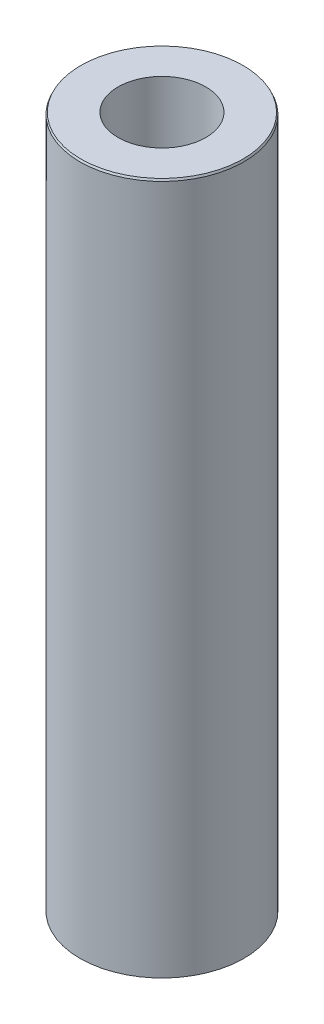
SolidWorks part; units mm, degrees
ref_plane "Front Plane" through (0, 0, 0) normal (0, 0, 1) x (1, 0, 0)
ref_plane "Top Plane" through (0, 0, 0) normal (0, 1, 0) x (1, 0, 0)
ref_plane "Right Plane" through (0, 0, 0) normal (1, 0, 0) x (0, 0, -1)
sketch "Sketch1" plane through (0, 0, 0) normal (0, 1, 0) x (1, 0, 0)
  circle A0 centre (0, 0) radius 60
  dimension "SHAFT_OD" = 120
extrude "Boss-Extrude1" add sketch "Sketch1" along normal blind 506.7565
sketch "Sketch2" plane through (0, 0, 0) normal (0, 1, 0) x (1, 0, 0)
  circle A0 centre (0, 0) radius 32.107
  dimension "BORE_D" = 64.214
extrude "Cut-Extrude1" cut sketch "Sketch2" along normal through all
chamfer "Chamfer1" distance 1.4488 angle 25.111 2 edges at (0, 506.7565, 60) (0, 0, 60) first distance on face at (0, 506.7565, 60) first distance on face at (0, 0, 32.107)
